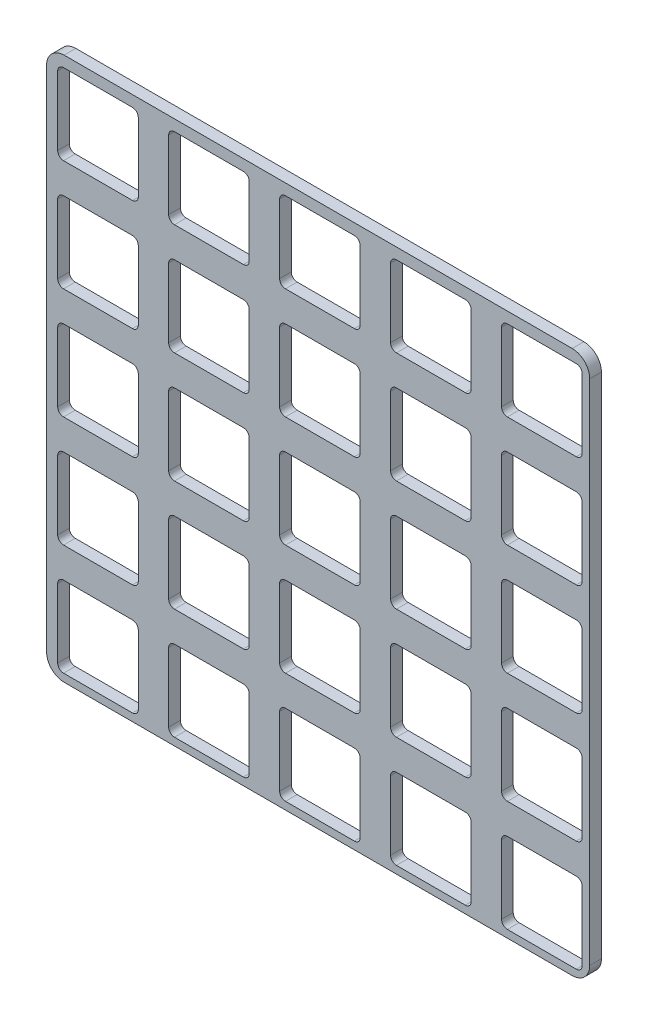
SolidWorks part; units mm, degrees
ref_plane "Front Plane" through (0, 0, 0) normal (0, 0, 1) x (1, 0, 0)
ref_plane "Top Plane" through (0, 0, 0) normal (0, 1, 0) x (1, 0, 0)
ref_plane "Right Plane" through (0, 0, 0) normal (1, 0, 0) x (0, 0, -1)
sketch "Sketch2" plane through (0, 0, 0) normal (0, 0, 1) x (1, 0, 0)
  line L0 (-43.5, 46.5) -> (43.5, 46.5)
  line L1 (-43.5, -47.5) -> (43.5, -47.5) construction
  line L2 (-47.5, -43.5) -> (-47.5, 43.5) construction
  line L3 (-43.5, 47.5) -> (43.5, 47.5) construction
  line L4 (47.5, -43.5) -> (47.5, 43.5) construction
  line L5 (-43.5, -43.5) -> (43.5, 43.5) construction
  line L6 (-43.5, 43.5) -> (43.5, -43.5) construction
  line L7 (46.5, -43.5) -> (46.5, 43.5)
  line L8 (-43.5, -46.5) -> (43.5, -46.5)
  line L9 (-46.5, -43.5) -> (-46.5, 43.5)
  line L10 (-25.6, 43.6) -> (-25.6, 31.8)
  line L11 (-43.6, 44.6) -> (-31.8, 44.6)
  line L12 (-44.6, 43.6) -> (-44.6, 31.8)
  line L13 (-43.6, 30.8) -> (-31.8, 30.8)
  line L14 (-30.8, 43.6) -> (-30.8, 31.8)
  line L15 (-24.6, 44.6) -> (-12.8, 44.6)
  line L16 (-11.8, 43.6) -> (-11.8, 31.8)
  line L17 (-24.6, 30.8) -> (-12.8, 30.8)
  line L18 (-6.6, 43.6) -> (-6.6, 31.8)
  line L19 (-5.6, 44.6) -> (6.2, 44.6)
  line L20 (7.2, 43.6) -> (7.2, 31.8)
  line L21 (-5.6, 30.8) -> (6.2, 30.8)
  line L22 (12.4, 43.6) -> (12.4, 31.8)
  line L23 (13.4, 44.6) -> (25.2, 44.6)
  line L24 (26.2, 43.6) -> (26.2, 31.8)
  line L25 (13.4, 30.8) -> (25.2, 30.8)
  line L26 (31.4, 43.6) -> (31.4, 31.8)
  line L27 (32.4, 44.6) -> (44.2, 44.6)
  line L28 (45.2, 43.6) -> (45.2, 31.8)
  line L29 (32.4, 30.8) -> (44.2, 30.8)
  line L30 (-25.6, 24.6) -> (-25.6, 12.8)
  line L31 (-24.6, 25.6) -> (-12.8, 25.6)
  line L32 (-11.8, 24.6) -> (-11.8, 12.8)
  line L33 (-24.6, 11.8) -> (-12.8, 11.8)
  line L34 (-6.6, 24.6) -> (-6.6, 12.8)
  line L35 (-5.6, 25.6) -> (6.2, 25.6)
  line L36 (7.2, 24.6) -> (7.2, 12.8)
  line L37 (-5.6, 11.8) -> (6.2, 11.8)
  line L38 (12.4, 24.6) -> (12.4, 12.8)
  line L39 (13.4, 25.6) -> (25.2, 25.6)
  line L40 (26.2, 24.6) -> (26.2, 12.8)
  line L41 (13.4, 11.8) -> (25.2, 11.8)
  line L42 (31.4, 24.6) -> (31.4, 12.8)
  line L43 (32.4, 25.6) -> (44.2, 25.6)
  line L44 (45.2, 24.6) -> (45.2, 12.8)
  line L45 (32.4, 11.8) -> (44.2, 11.8)
  line L46 (-25.6, 5.6) -> (-25.6, -6.2)
  line L47 (-24.6, 6.6) -> (-12.8, 6.6)
  line L48 (-11.8, 5.6) -> (-11.8, -6.2)
  line L49 (-24.6, -7.2) -> (-12.8, -7.2)
  line L50 (-6.6, 5.6) -> (-6.6, -6.2)
  line L51 (-5.6, 6.6) -> (6.2, 6.6)
  line L52 (7.2, 5.6) -> (7.2, -6.2)
  line L53 (-5.6, -7.2) -> (6.2, -7.2)
  line L54 (12.4, 5.6) -> (12.4, -6.2)
  line L55 (13.4, 6.6) -> (25.2, 6.6)
  line L56 (26.2, 5.6) -> (26.2, -6.2)
  line L57 (13.4, -7.2) -> (25.2, -7.2)
  line L58 (31.4, 5.6) -> (31.4, -6.2)
  line L59 (32.4, 6.6) -> (44.2, 6.6)
  line L60 (45.2, 5.6) -> (45.2, -6.2)
  line L61 (32.4, -7.2) -> (44.2, -7.2)
  line L62 (-25.6, -13.4) -> (-25.6, -25.2)
  line L63 (-24.6, -12.4) -> (-12.8, -12.4)
  line L64 (-11.8, -13.4) -> (-11.8, -25.2)
  line L65 (-24.6, -26.2) -> (-12.8, -26.2)
  line L66 (-6.6, -13.4) -> (-6.6, -25.2)
  line L67 (-5.6, -12.4) -> (6.2, -12.4)
  line L68 (7.2, -13.4) -> (7.2, -25.2)
  line L69 (-5.6, -26.2) -> (6.2, -26.2)
  line L70 (12.4, -13.4) -> (12.4, -25.2)
  line L71 (13.4, -12.4) -> (25.2, -12.4)
  line L72 (26.2, -13.4) -> (26.2, -25.2)
  line L73 (13.4, -26.2) -> (25.2, -26.2)
  line L74 (31.4, -13.4) -> (31.4, -25.2)
  line L75 (32.4, -12.4) -> (44.2, -12.4)
  line L76 (45.2, -13.4) -> (45.2, -25.2)
  line L77 (32.4, -26.2) -> (44.2, -26.2)
  line L78 (-25.6, -32.4) -> (-25.6, -44.2)
  line L79 (-24.6, -31.4) -> (-12.8, -31.4)
  line L80 (-11.8, -32.4) -> (-11.8, -44.2)
  line L81 (-24.6, -45.2) -> (-12.8, -45.2)
  line L82 (-6.6, -32.4) -> (-6.6, -44.2)
  line L83 (-5.6, -31.4) -> (6.2, -31.4)
  line L84 (7.2, -32.4) -> (7.2, -44.2)
  line L85 (-5.6, -45.2) -> (6.2, -45.2)
  line L86 (12.4, -32.4) -> (12.4, -44.2)
  line L87 (13.4, -31.4) -> (25.2, -31.4)
  line L88 (26.2, -32.4) -> (26.2, -44.2)
  line L89 (13.4, -45.2) -> (25.2, -45.2)
  line L90 (31.4, -32.4) -> (31.4, -44.2)
  line L91 (32.4, -31.4) -> (44.2, -31.4)
  line L92 (45.2, -32.4) -> (45.2, -44.2)
  line L93 (32.4, -45.2) -> (44.2, -45.2)
  line L94 (-44.6, 24.6) -> (-44.6, 12.8)
  line L95 (-43.6, 25.6) -> (-31.8, 25.6)
  line L96 (-30.8, 24.6) -> (-30.8, 12.8)
  line L97 (-43.6, 11.8) -> (-31.8, 11.8)
  line L98 (-44.6, 5.6) -> (-44.6, -6.2)
  line L99 (-43.6, 6.6) -> (-31.8, 6.6)
  line L100 (-30.8, 5.6) -> (-30.8, -6.2)
  line L101 (-43.6, -7.2) -> (-31.8, -7.2)
  line L102 (-44.6, -13.4) -> (-44.6, -25.2)
  line L103 (-43.6, -12.4) -> (-31.8, -12.4)
  line L104 (-30.8, -13.4) -> (-30.8, -25.2)
  line L105 (-43.6, -26.2) -> (-31.8, -26.2)
  line L106 (-44.6, -32.4) -> (-44.6, -44.2)
  line L107 (-43.6, -31.4) -> (-31.8, -31.4)
  line L108 (-30.8, -32.4) -> (-30.8, -44.2)
  line L109 (-43.6, -45.2) -> (-31.8, -45.2)
  line L110 (-44.6, 43.6) -> (-25.6, 43.6) construction
  line L111 (-44.6, 43.6) -> (-44.6, 24.6) construction
  arc A0 (-43.5, -47.5) -> (-47.5, -43.5) centre (-43.5, -43.5) cw construction
  arc A1 (43.5, -47.5) -> (47.5, -43.5) centre (43.5, -43.5) ccw construction
  arc A2 (43.5, 47.5) -> (47.5, 43.5) centre (43.5, 43.5) cw construction
  arc A3 (-47.5, 43.5) -> (-43.5, 47.5) centre (-43.5, 43.5) cw construction
  arc A4 (43.5, 46.5) -> (46.5, 43.5) centre (43.5, 43.5) cw
  arc A5 (43.5, -46.5) -> (46.5, -43.5) centre (43.5, -43.5) ccw
  arc A6 (-43.5, -46.5) -> (-46.5, -43.5) centre (-43.5, -43.5) cw
  arc A7 (-46.5, 43.5) -> (-43.5, 46.5) centre (-43.5, 43.5) cw
  arc A8 (-44.6, 31.8) -> (-43.6, 30.8) centre (-43.6, 31.8) ccw
  arc A9 (-31.8, 30.8) -> (-30.8, 31.8) centre (-31.8, 31.8) ccw
  arc A10 (-31.8, 44.6) -> (-30.8, 43.6) centre (-31.8, 43.6) cw
  arc A11 (-43.6, 44.6) -> (-44.6, 43.6) centre (-43.6, 43.6) ccw
  arc A12 (-24.6, 44.6) -> (-25.6, 43.6) centre (-24.6, 43.6) ccw
  arc A13 (-25.6, 31.8) -> (-24.6, 30.8) centre (-24.6, 31.8) ccw
  arc A14 (-12.8, 44.6) -> (-11.8, 43.6) centre (-12.8, 43.6) cw
  arc A15 (-12.8, 30.8) -> (-11.8, 31.8) centre (-12.8, 31.8) ccw
  arc A16 (-5.6, 44.6) -> (-6.6, 43.6) centre (-5.6, 43.6) ccw
  arc A17 (-6.6, 31.8) -> (-5.6, 30.8) centre (-5.6, 31.8) ccw
  arc A18 (6.2, 44.6) -> (7.2, 43.6) centre (6.2, 43.6) cw
  arc A19 (6.2, 30.8) -> (7.2, 31.8) centre (6.2, 31.8) ccw
  arc A20 (13.4, 44.6) -> (12.4, 43.6) centre (13.4, 43.6) ccw
  arc A21 (12.4, 31.8) -> (13.4, 30.8) centre (13.4, 31.8) ccw
  arc A22 (25.2, 44.6) -> (26.2, 43.6) centre (25.2, 43.6) cw
  arc A23 (25.2, 30.8) -> (26.2, 31.8) centre (25.2, 31.8) ccw
  arc A24 (32.4, 44.6) -> (31.4, 43.6) centre (32.4, 43.6) ccw
  arc A25 (31.4, 31.8) -> (32.4, 30.8) centre (32.4, 31.8) ccw
  arc A26 (44.2, 44.6) -> (45.2, 43.6) centre (44.2, 43.6) cw
  arc A27 (44.2, 30.8) -> (45.2, 31.8) centre (44.2, 31.8) ccw
  arc A28 (-24.6, 25.6) -> (-25.6, 24.6) centre (-24.6, 24.6) ccw
  arc A29 (-25.6, 12.8) -> (-24.6, 11.8) centre (-24.6, 12.8) ccw
  arc A30 (-12.8, 25.6) -> (-11.8, 24.6) centre (-12.8, 24.6) cw
  arc A31 (-12.8, 11.8) -> (-11.8, 12.8) centre (-12.8, 12.8) ccw
  arc A32 (-5.6, 25.6) -> (-6.6, 24.6) centre (-5.6, 24.6) ccw
  arc A33 (-6.6, 12.8) -> (-5.6, 11.8) centre (-5.6, 12.8) ccw
  arc A34 (6.2, 25.6) -> (7.2, 24.6) centre (6.2, 24.6) cw
  arc A35 (6.2, 11.8) -> (7.2, 12.8) centre (6.2, 12.8) ccw
  arc A36 (13.4, 25.6) -> (12.4, 24.6) centre (13.4, 24.6) ccw
  arc A37 (12.4, 12.8) -> (13.4, 11.8) centre (13.4, 12.8) ccw
  arc A38 (25.2, 25.6) -> (26.2, 24.6) centre (25.2, 24.6) cw
  arc A39 (25.2, 11.8) -> (26.2, 12.8) centre (25.2, 12.8) ccw
  arc A40 (32.4, 25.6) -> (31.4, 24.6) centre (32.4, 24.6) ccw
  arc A41 (31.4, 12.8) -> (32.4, 11.8) centre (32.4, 12.8) ccw
  arc A42 (44.2, 25.6) -> (45.2, 24.6) centre (44.2, 24.6) cw
  arc A43 (44.2, 11.8) -> (45.2, 12.8) centre (44.2, 12.8) ccw
  arc A44 (-24.6, 6.6) -> (-25.6, 5.6) centre (-24.6, 5.6) ccw
  arc A45 (-25.6, -6.2) -> (-24.6, -7.2) centre (-24.6, -6.2) ccw
  arc A46 (-12.8, 6.6) -> (-11.8, 5.6) centre (-12.8, 5.6) cw
  arc A47 (-12.8, -7.2) -> (-11.8, -6.2) centre (-12.8, -6.2) ccw
  arc A48 (-5.6, 6.6) -> (-6.6, 5.6) centre (-5.6, 5.6) ccw
  arc A49 (-6.6, -6.2) -> (-5.6, -7.2) centre (-5.6, -6.2) ccw
  arc A50 (6.2, 6.6) -> (7.2, 5.6) centre (6.2, 5.6) cw
  arc A51 (6.2, -7.2) -> (7.2, -6.2) centre (6.2, -6.2) ccw
  arc A52 (13.4, 6.6) -> (12.4, 5.6) centre (13.4, 5.6) ccw
  arc A53 (12.4, -6.2) -> (13.4, -7.2) centre (13.4, -6.2) ccw
  arc A54 (25.2, 6.6) -> (26.2, 5.6) centre (25.2, 5.6) cw
  arc A55 (25.2, -7.2) -> (26.2, -6.2) centre (25.2, -6.2) ccw
  arc A56 (32.4, 6.6) -> (31.4, 5.6) centre (32.4, 5.6) ccw
  arc A57 (31.4, -6.2) -> (32.4, -7.2) centre (32.4, -6.2) ccw
  arc A58 (44.2, 6.6) -> (45.2, 5.6) centre (44.2, 5.6) cw
  arc A59 (44.2, -7.2) -> (45.2, -6.2) centre (44.2, -6.2) ccw
  arc A60 (-24.6, -12.4) -> (-25.6, -13.4) centre (-24.6, -13.4) ccw
  arc A61 (-25.6, -25.2) -> (-24.6, -26.2) centre (-24.6, -25.2) ccw
  arc A62 (-12.8, -12.4) -> (-11.8, -13.4) centre (-12.8, -13.4) cw
  arc A63 (-12.8, -26.2) -> (-11.8, -25.2) centre (-12.8, -25.2) ccw
  arc A64 (-5.6, -12.4) -> (-6.6, -13.4) centre (-5.6, -13.4) ccw
  arc A65 (-6.6, -25.2) -> (-5.6, -26.2) centre (-5.6, -25.2) ccw
  arc A66 (6.2, -12.4) -> (7.2, -13.4) centre (6.2, -13.4) cw
  arc A67 (6.2, -26.2) -> (7.2, -25.2) centre (6.2, -25.2) ccw
  arc A68 (13.4, -12.4) -> (12.4, -13.4) centre (13.4, -13.4) ccw
  arc A69 (12.4, -25.2) -> (13.4, -26.2) centre (13.4, -25.2) ccw
  arc A70 (25.2, -12.4) -> (26.2, -13.4) centre (25.2, -13.4) cw
  arc A71 (25.2, -26.2) -> (26.2, -25.2) centre (25.2, -25.2) ccw
  arc A72 (32.4, -12.4) -> (31.4, -13.4) centre (32.4, -13.4) ccw
  arc A73 (31.4, -25.2) -> (32.4, -26.2) centre (32.4, -25.2) ccw
  arc A74 (44.2, -12.4) -> (45.2, -13.4) centre (44.2, -13.4) cw
  arc A75 (44.2, -26.2) -> (45.2, -25.2) centre (44.2, -25.2) ccw
  arc A76 (-24.6, -31.4) -> (-25.6, -32.4) centre (-24.6, -32.4) ccw
  arc A77 (-25.6, -44.2) -> (-24.6, -45.2) centre (-24.6, -44.2) ccw
  arc A78 (-12.8, -31.4) -> (-11.8, -32.4) centre (-12.8, -32.4) cw
  arc A79 (-12.8, -45.2) -> (-11.8, -44.2) centre (-12.8, -44.2) ccw
  arc A80 (-5.6, -31.4) -> (-6.6, -32.4) centre (-5.6, -32.4) ccw
  arc A81 (-6.6, -44.2) -> (-5.6, -45.2) centre (-5.6, -44.2) ccw
  arc A82 (6.2, -31.4) -> (7.2, -32.4) centre (6.2, -32.4) cw
  arc A83 (6.2, -45.2) -> (7.2, -44.2) centre (6.2, -44.2) ccw
  arc A84 (13.4, -31.4) -> (12.4, -32.4) centre (13.4, -32.4) ccw
  arc A85 (12.4, -44.2) -> (13.4, -45.2) centre (13.4, -44.2) ccw
  arc A86 (25.2, -31.4) -> (26.2, -32.4) centre (25.2, -32.4) cw
  arc A87 (25.2, -45.2) -> (26.2, -44.2) centre (25.2, -44.2) ccw
  arc A88 (32.4, -31.4) -> (31.4, -32.4) centre (32.4, -32.4) ccw
  arc A89 (31.4, -44.2) -> (32.4, -45.2) centre (32.4, -44.2) ccw
  arc A90 (44.2, -31.4) -> (45.2, -32.4) centre (44.2, -32.4) cw
  arc A91 (44.2, -45.2) -> (45.2, -44.2) centre (44.2, -44.2) ccw
  arc A92 (-43.6, 25.6) -> (-44.6, 24.6) centre (-43.6, 24.6) ccw
  arc A93 (-44.6, 12.8) -> (-43.6, 11.8) centre (-43.6, 12.8) ccw
  arc A94 (-31.8, 25.6) -> (-30.8, 24.6) centre (-31.8, 24.6) cw
  arc A95 (-31.8, 11.8) -> (-30.8, 12.8) centre (-31.8, 12.8) ccw
  arc A96 (-43.6, 6.6) -> (-44.6, 5.6) centre (-43.6, 5.6) ccw
  arc A97 (-44.6, -6.2) -> (-43.6, -7.2) centre (-43.6, -6.2) ccw
  arc A98 (-31.8, 6.6) -> (-30.8, 5.6) centre (-31.8, 5.6) cw
  arc A99 (-31.8, -7.2) -> (-30.8, -6.2) centre (-31.8, -6.2) ccw
  arc A100 (-43.6, -12.4) -> (-44.6, -13.4) centre (-43.6, -13.4) ccw
  arc A101 (-44.6, -25.2) -> (-43.6, -26.2) centre (-43.6, -25.2) ccw
  arc A102 (-31.8, -12.4) -> (-30.8, -13.4) centre (-31.8, -13.4) cw
  arc A103 (-31.8, -26.2) -> (-30.8, -25.2) centre (-31.8, -25.2) ccw
  arc A104 (-43.6, -31.4) -> (-44.6, -32.4) centre (-43.6, -32.4) ccw
  arc A105 (-44.6, -44.2) -> (-43.6, -45.2) centre (-43.6, -44.2) ccw
  arc A106 (-31.8, -31.4) -> (-30.8, -32.4) centre (-31.8, -32.4) cw
  arc A107 (-31.8, -45.2) -> (-30.8, -44.2) centre (-31.8, -44.2) ccw
  point P0 (0, 0)
  dimension "D1" = 4
  dimension "D4" = 1
  dimension "D2" = 95
  dimension "D5" = 13.8
  dimension "D6" = 2.9
  dimension "D9" = 90
  dimension "D10" = 19
  dimension "D11" = 19
  dimension "D3" = 1
  dimension "D7" = 5
  dimension "D8" = 5
extrude "Boss-Extrude1" add sketch "Sketch2" along normal blind 2
